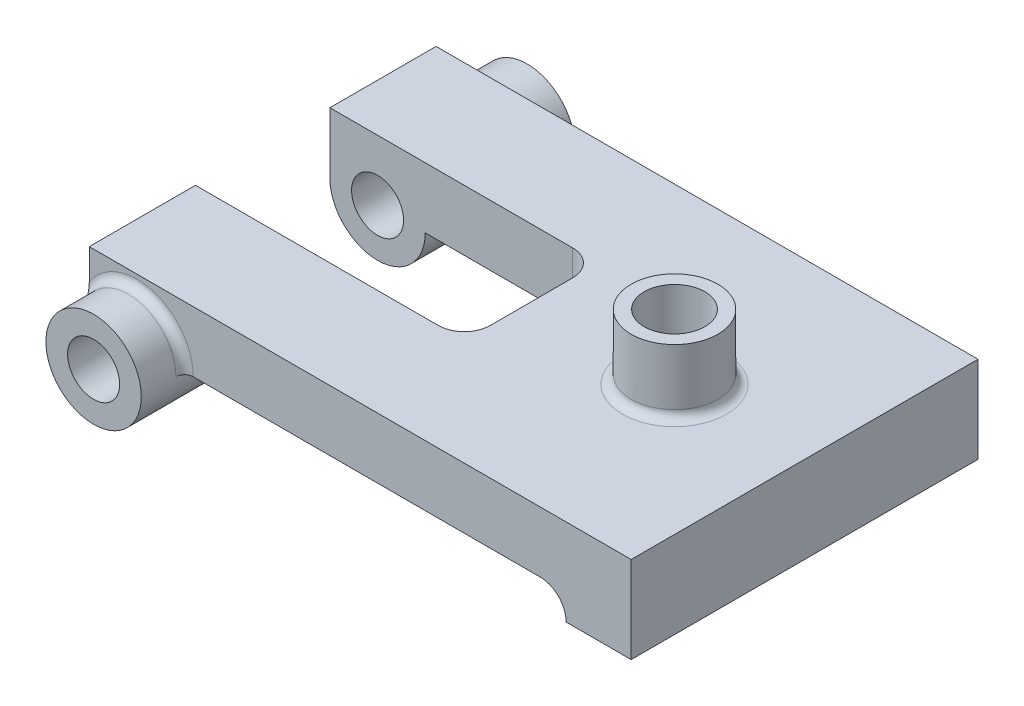
SolidWorks part; units mm, degrees
ref_plane "Front Plane" through (0, 0, 0) normal (0, 0, 1) x (1, 0, 0)
ref_plane "Top Plane" through (0, 0, 0) normal (0, 1, 0) x (1, 0, 0)
ref_plane "Right Plane" through (0, 0, 0) normal (1, 0, 0) x (0, 0, -1)
sketch "Sketch1" plane through (0, 0, 0) normal (0, 1, 0) x (1, 0, 0)
  line L0 (-62.5, 0) -> (38.8769, 0) construction
  line L1 (-62.5, -50) -> (-40.5, -50)
  line L2 (-62.5, -50) -> (-62.5, 50)
  line L3 (-62.5, 50) -> (-40.5, 50)
  line L4 (62.5, -40) -> (62.5, 40)
  line L5 (-62.5, -50) -> (50, 40) construction
  line L6 (-62.5, 50) -> (50, -40) construction
  line L7 (-62.5, 50) -> (-40.5, 50)
  line L8 (-62.5, 50) -> (-62.5, -50)
  line L9 (-62.5, -50) -> (-40.5, -50)
  line L10 (-40.5, 50) -> (-40.5, 42)
  line L11 (50, 40) -> (62.5, 40)
  line L13 (-38.5, -40) -> (62.5, -40)
  line L14 (62.5, 40) -> (62.5, -40)
  line L15 (-38.5, 40) -> (50, 40)
  line L16 (-40.5, -42) -> (-40.5, -50)
  arc A0 (-40.5, -42) -> (-38.5, -40) centre (-38.5, -42) cw
  arc A1 (-38.5, 40) -> (-40.5, 42) centre (-38.5, 42) cw
  point P0 (0, 0)
  point P14 (0, 0)
  dimension "D5" = 2
  dimension "D2" = 100
  dimension "D3" = 22
  dimension "D4" = 80
extrude "Boss-Extrude1" add sketch "Sketch1" along normal blind 40 contours L15 A1 L10 L3 L2 L1 L16 A0 L13 L4 L11 region at (-2.1767, 0, 0)
sketch "Sketch2" plane through (0, 0, 0) normal (0, 0, 1) x (1, 0, 0)
  line L0 (-62.5, 40) -> (-62.5, 0) construction
  line L1 (-62.5, 20) -> (43.2608, 20)
  line L2 (-62.5, 20) -> (-62.5, 6)
  line L3 (-62.5, 6) -> (47.5, 6)
  line L4 (62.5, 20) -> (62.5, 6)
  line L5 (62.5, 40) -> (62.5, 0) construction
  line L8 (47.5, 6) -> (47.5, 0)
  line L9 (47.5, 0) -> (62.5, 0)
  line L10 (62.5, 6) -> (62.5, 0)
  line L16 (42.5, 20) -> (62.5, 20)
  circle A0 centre (-51.5, 6) radius 11
  point P13 (43.2608, 20)
  dimension "D1" = 22
  dimension "D2" = 20
  dimension "D3" = 14
  dimension "D4" = 15
extrude "Cut-Extrude1" cut sketch "Sketch2" against normal through all both and the other way through all flip side to cut contours L3 A0 | L3 A0 | A0 L3 L4 L1 L2 | L1 | L10 L3 L8 L9 region at (8.9327, 12.7231, 0) region at (-51.5, 10.6685, 0) region at (-51.5, 1.3315, 0)
extrude "Boss-Extrude2" add sketch "Sketch2<3>" against normal up to surface and the other way up to surface contours L3 A0 region at (-51.5, 1.3315, 0) up to face at (-51.5, 8.6236, -50) other way up to face at (-51.5, 8.6236, 50)
sketch "Sketch2<3>" plane through (0, 0, 0) normal (0, 0, 1) x (1, 0, 0) same geometry as "Sketch2"
sketch "Sketch3" plane through (0, 0, 50) normal (0, 0, 1) x (1, 0, 0)
  circle A0 centre (-51.5, 6) radius 6
  point P3 (0, 0)
  point P4 (-50.8806, 3.9359)
  point P8 (-51.5, 6)
  dimension "D1" = 12
extrude "Cut-Extrude2" cut sketch "Sketch3" against normal through all both and the other way through all
sketch "Sketch4" plane through (-62.5, 0, 0) normal (-1, 0, 0) x (0, 0, 1)
  line L8 (-15.5, -5) -> (15.5, -5)
  line L10 (-15.5, -5) -> (-15.5, 20)
  line L11 (15.5, 20) -> (15.5, -5)
  line L15 (-15.5, 20) -> (15.5, 20)
  line L17 (-50, 20) -> (50, 20) construction
  point P7 (0, 0)
  dimension "D1" = 25
  dimension "D2" = 31
extrude "Cut-Extrude3" cut sketch "Sketch4" against normal blind 62 contours L8 | L11 L8 L10 L15 region at (-62.5, 7.5, 0)
sketch "Sketch5" plane through (0, 20, 0) normal (0, 1, 0) x (1, 0, 0)
  line L0 (62.5, 40) -> (62.5, -40) construction
  circle A0 centre (32.5, -0.0026) radius 10
  circle A1 centre (32.5, -0.0026) radius 7
  dimension "D1" = 20
  dimension "D2" = 30
  dimension "D3" = 3
extrude "Boss-Extrude3" add sketch "Sketch5" along normal blind 15 contours A0 A1 | A0 | A1 region at (22.7828, 20, 0.0026)
sketch "Sketch6" plane through (0, 0, 50) normal (0, 0, 1) x (1, 0, 0)
  line L1 (-38.5, 20) -> (-62.5, 20)
  line L2 (-38.5, 20) -> (-38.5, 6)
  line L3 (-38.5, 6) -> (-40.5, 6)
  line L4 (-62.5, 20) -> (-62.5, 6)
  arc A0 (-40.5, 6) -> (-62.5, 6) centre (-51.5, 6) ccw
extrude "Cut-Extrude4" cut sketch "Sketch6" against normal blind 10
mirror "Mirror1" about plane through (0, 0, 0) normal (0, 0, 1) of "Cut-Extrude4"
fillet "Fillet2" radius 2 3 edges at (42.5, 20, 0.0026) (-51.5, 17, -40) (-51.5, 17, 40)
fillet "Fillet1" radius 6 3 edges at (47.5, 6, 0) (-0.5, 13, -15.5) (-0.5, 13, 15.5)
sketch "Sketch7" plane through (0, 20, 0) normal (0, 1, 0) x (1, 0, 0)
  circle A0 centre (32.5, -0.0026) radius 8
extrude "Cut-Extrude5" cut sketch "Sketch7" against normal through all
